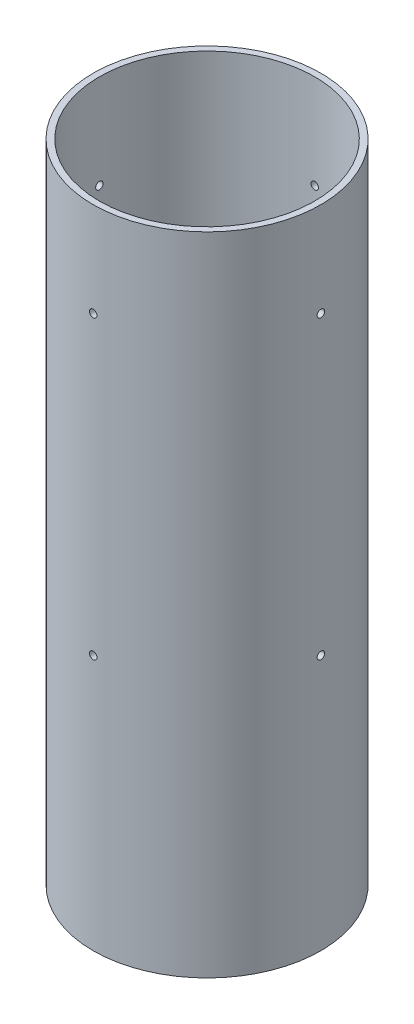
SolidWorks part; units mm, degrees
material "E-Glass Fiber"
ref_plane "Front Plane" through (0, 0, 0) normal (0, 0, 1) x (1, 0, 0)
ref_plane "Top Plane" through (0, 0, 0) normal (0, 1, 0) x (1, 0, 0)
ref_plane "Right Plane" through (0, 0, 0) normal (1, 0, 0) x (0, 0, -1)
sketch "Sketch1" plane through (0, 0, 0) normal (0, 1, 0) x (1, 0, 0)
  circle A0 centre (0, 0) radius 53.721
  circle A1 centre (0, 0) radius 50.8
  dimension "D1" = 107.442
  dimension "D2" = 101.6
extrude "Boss-Extrude1" add sketch "Sketch1" along normal blind 304.8
sketch "Sketch2" plane through (0, 0, 0) normal (0, 0, 1) x (1, 0, 0)
  line L2 (0, 0) -> (0, 120.65)
  circle A0 centre (0, 120.65) radius 1.7526
  dimension "D2" = 3.5052
  dimension "D1" = 120.65
extrude "Bulkhead Holes" cut sketch "Sketch2" against normal blind 127 contours A0
pattern_circular "CirPattern1" count 4 over 360 about axis through (0, 304.8, 0) along (0, -1, 0) of "Bulkhead Holes" reverse direction yes
ref_plane "Plane1" through (53.721, 0, 0) normal (1, 0, 0) x (0, 0, -1)
sketch "Sketch3" plane through (53.721, 0, 0) normal (1, 0, 0) x (0, 0, -1)
  line L0 (0, 0) -> (0, 304.8) construction
  line L1 (-53.721, 0) -> (53.721, 0) construction
  line L2 (50.8, 304.8) -> (-50.8, 304.8) construction
  line L3 (53.721, 304.8) -> (-53.721, 304.8) construction
  circle A0 centre (0, 260.35) radius 1.7526
  dimension "D1" = 3.5052
  dimension "D2" = 44.45
extrude "Cut-Extrude1" cut sketch "Sketch3" against normal up to next
pattern_circular "CirPattern2" count 4 over 360 about axis through (0, 304.8, 0) along (0, -1, 0) of "Cut-Extrude1"
